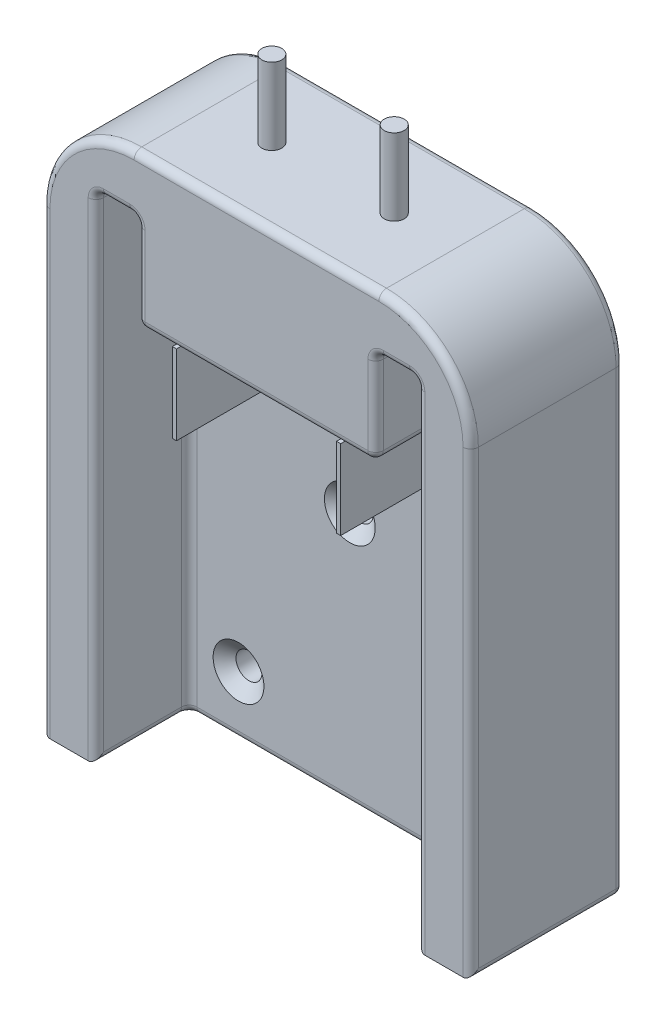
SolidWorks part; units mm, degrees
material "ABS PC"
ref_plane "Front Plane" through (0, 0, 0) normal (0, 0, 1) x (1, 0, 0)
ref_plane "Top Plane" through (0, 0, 0) normal (0, 1, 0) x (1, 0, 0)
ref_plane "Right Plane" through (0, 0, 0) normal (1, 0, 0) x (0, 0, -1)
sketch "Sketch3" plane through (0, 0, 0) normal (0, 0, 1) x (1, 0, 0)
  line L1 (35.56, 45.72) -> (-35.56, 45.72)
  line L2 (35.56, 45.72) -> (35.56, -45.72)
  line L3 (35.56, -45.72) -> (-35.56, -45.72)
  line L4 (-35.56, 45.72) -> (-35.56, -45.72)
  line L5 (35.56, 45.72) -> (-35.56, -45.72) construction
  line L6 (35.56, -45.72) -> (-35.56, 45.72) construction
  point P0 (0, 0)
  dimension "D1" = 71.12
  dimension "D2" = 91.44
extrude "Boss-Extrude1" add sketch "Sketch3" along normal blind 25.4
sketch "Sketch4" plane through (0, 0, 25.4) normal (0, 0, 1) x (1, 0, 0)
  line L0 (-35.56, -45.72) -> (-26.67, -45.72) construction
  line L1 (-35.56, -45.72) -> (35.56, -45.72) construction
  line L2 (-26.67, -45.72) -> (-26.67, 20.828)
  line L3 (-19.7739, 20.828) -> (19.7739, 20.828)
  line L4 (26.67, 20.828) -> (26.67, -45.72)
  line L5 (0, 45.72) -> (0, -45.72) construction
  line L6 (35.56, 45.72) -> (-35.56, 45.72) construction
  line L8 (-26.67, 20.828) -> (-26.67, 36.5125)
  line L9 (-26.67, 36.5125) -> (-19.7739, 36.5125)
  line L10 (-19.7739, 36.5125) -> (-19.7739, 20.828)
  line L11 (26.67, 20.828) -> (26.67, 36.5125)
  line L12 (19.7739, 36.5125) -> (19.7739, 20.828)
  line L13 (26.67, 36.5125) -> (19.7739, 36.5125)
  line L14 (-13.97, 20.828) -> (-13.97, 7.62)
  line L15 (-13.97, 7.62) -> (-13.2842, 7.62)
  line L16 (-13.2842, 7.62) -> (-13.2842, 20.828)
  line L17 (-26.67, -45.72) -> (26.67, -45.72)
  line L18 (13.2842, 7.62) -> (13.2842, 20.828)
  line L19 (13.97, 7.62) -> (13.2842, 7.62)
  line L20 (13.97, 20.828) -> (13.97, 7.62)
  dimension "D1" = 53.34
  dimension "D2" = 24.892
  dimension "D3" = 15.6845
  dimension "D4" = 6.8961
  dimension "D5" = 0.6858
  dimension "D6" = 13.208
  dimension "D7" = 12.7
extrude "Cut-Extrude1" cut sketch "Sketch4" against normal offset from surface (15.494 mm away) 9.906 contours L3 L12 L13 L11 L4 L17 L2 L8 L9 L10 up to face at (0, 0, 0)
sketch "Sketch7" plane through (0, 0, 25.4) normal (0, 0, 1) x (1, 0, 0)
  line L0 (13.97, 7.62) -> (13.2842, 7.62) construction
  line L1 (13.97, 20.828) -> (13.97, 7.62) construction
  line L2 (13.2842, 7.62) -> (13.2842, 20.828) construction
  line L3 (-13.97, 7.62) -> (-13.2842, 7.62) construction
  line L4 (-13.97, 20.828) -> (-13.97, 7.62) construction
  line L5 (-13.2842, 7.62) -> (-13.2842, 20.828) construction
  line L6 (13.97, 7.62) -> (13.2842, 7.62)
  line L7 (13.97, 20.828) -> (13.97, 7.62)
  line L8 (13.2842, 7.62) -> (13.2842, 20.828)
  line L9 (-13.97, 7.62) -> (-13.2842, 7.62)
  line L10 (-13.97, 20.828) -> (-13.97, 7.62)
  line L11 (-13.2842, 7.62) -> (-13.2842, 20.828)
  line L12 (-13.97, 20.828) -> (-13.2842, 20.828)
  line L13 (13.2842, 20.828) -> (13.97, 20.828)
extrude "Boss-Extrude2" add sketch "Sketch7" against normal up to surface (15.494 mm away) separate body up to face at (0, 12.0332, 9.906)
sketch "Sketch8" plane through (0, 0, 9.906) normal (0, 0, 1) x (1, 0, 0)
  line L0 (0, 45.72) -> (0, -45.72) construction
  line L1 (35.56, 45.72) -> (-35.56, 45.72) construction
  line L2 (-26.67, -45.72) -> (26.67, -45.72) construction
  line L5 (-18.4775, -37.9603) -> (-18.4775, -45.72) construction
  circle A0 centre (0, -25.2603) radius 21.336 construction
  circle A1 centre (0, -3.9243) radius 2.032
  circle A2 centre (18.4775, -35.9283) radius 2.032
  circle A3 centre (-18.4775, -35.9283) radius 2.032
  dimension "D1" = 42.672
  dimension "D2" = 4.064
  dimension "D5" = 7.7597
  dimension "D3" = 3
hole_wizard "CSK for #8 Flat Head Machine Screw (100)1" positions "Sketch9" profile "Sketch10" countersink size "#8" standard "ANSI Inch" end condition through all
sketch "Sketch9" plane through (0, 0, 9.906) normal (0, 0, 1) x (1, 0, 0)
  point P0 (0, -3.9243)
  point P3 (-18.4775, -35.9283)
  point P6 (18.4775, -35.9283)
sketch "Sketch10" plane through (0, -3.9243, 9.906) normal (1, 0, 0) x (0, -1, 0)
  line L0 (0, 0) -> (0, 9.906)
  line L1 (0, 9.906) -> (2.1526, 9.906)
  line L2 (2.1526, 9.906) -> (2.1526, 1.7317)
  line L3 (2.1526, 1.7317) -> (4.2164, 0)
  line L5 (4.2164, 0) -> (0, 0)
  line L6 (-2.1526, 1.7317) -> (-4.2164, 0) construction
  line L11 (0, -6.35) -> (0, 107.95) construction
  dimension "Thru Hole Dia." = 4.3053
  dimension "Thru Hole Depth" = 9.906
  dimension "Near C'Sink Dia." = 8.4328
  dimension "Near C'Sink Angle" = 100
fillet "Fillet1" radius 15.24 2 edges at (35.56, 45.72, 12.7) (-35.56, 45.72, 12.7)
fillet "Fillet2" radius 1.27 36 edges at (35.56, -7.62, 0) (31.0963, 41.2563, 0) (0, 45.72, 0) (-31.0963, 41.2563, 0) (-35.56, -7.62, 25.4) (-31.0963, 41.2563, 25.4) (0, 45.72, 25.4) (31.0963, 41.2563, 25.4) (-35.56, -7.62, 0) (0, -45.72, 0) (0, -45.72, 9.906) (35.56, -7.62, 25.4) (35.56, -45.72, 12.7) (-35.56, -45.72, 12.7) (-26.67, -45.72, 17.653) (26.67, -45.72, 17.653) (19.7739, 36.5125, 17.653) (26.67, 36.5125, 17.653) (19.7739, 20.828, 17.653) (-19.7739, 36.5125, 17.653) (-19.7739, 20.828, 17.653) (-26.67, 36.5125, 17.653) (26.67, -4.6038, 25.4) (-26.67, -4.6038, 25.4) (-19.7739, 28.6702, 9.906) (19.7739, 28.6702, 9.906) (23.2219, 36.5125, 25.4) (-23.2219, 36.5125, 25.4) (23.2219, 36.5125, 9.906) (-23.2219, 36.5125, 9.906) (-26.67, -4.6038, 9.906) (26.67, -4.6038, 9.906) (0, 20.828, 9.906) (0, 20.828, 25.4) (19.7739, 28.6702, 25.4) (-19.7739, 28.6702, 25.4)
sketch "Sketch11" plane through (0, 45.72, 0) normal (0, 1, 0) x (1, 0, 0)
  line L0 (-20.32, -12.7) -> (0, -12.7) construction
  line L3 (0, 0) -> (0, -24.13) construction
  line L4 (-20.32, 0) -> (20.32, 0) construction
  line L5 (-20.32, -24.13) -> (20.32, -24.13) construction
  line L6 (-20.32, -1.27) -> (-20.32, -24.13) construction
  circle A0 centre (-10.16, -12.7) radius 1.651
  circle A1 centre (10.16, -12.7) radius 1.651
  point P16 (-10.16, -12.7)
  dimension "D1" = 3.302
extrude "Boss-Extrude3" add sketch "Sketch11" along normal blind 12.7 separate body
